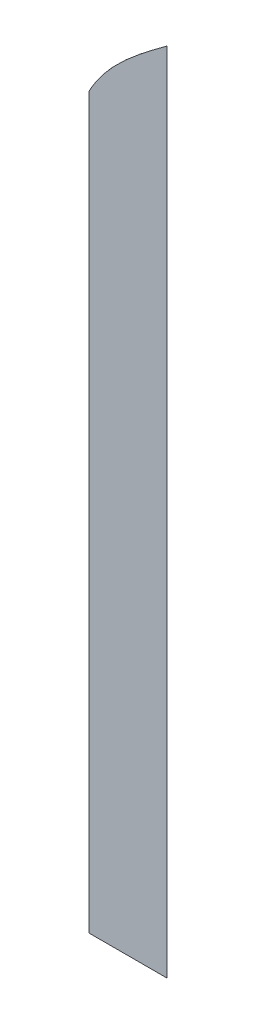
SolidWorks part; units mm, degrees
material "PC High Viscosity"
ref_plane "Front Plane" through (0, 0, 0) normal (0, 0, 1) x (1, 0, 0)
ref_plane "Top Plane" through (0, 0, 0) normal (0, 1, 0) x (1, 0, 0)
ref_plane "Right Plane" through (0, 0, 0) normal (1, 0, 0) x (0, 0, -1)
sketch "Sketch1" plane through (0, 0, 0) normal (0, 0, 1) x (1, 0, 0)
  line L0 (0, 1651) -> (0, 0)
  line L1 (0, 0) -> (-723.9, 0)
  line L4 (-443.5701, 489.6368) -> (-684.6697, 175.2064)
  line L5 (-709.936, 113.4438) -> (-723.9, 0)
  arc A1 (-684.6697, 175.2064) -> (-709.936, 113.4438) centre (-583.8873, 97.9283) ccw
  spline S0 degree 3 poles (-443.5701, 489.6368) (-241.6604, 752.9576) (-282.7431, 676.9444) (0, 1651) knots 0 0 0 0 1 1 1 1
  dimension "D3" = 127
  dimension "D1" = 1651
  dimension "D5" = 114.3
  dimension "D6" = 723.9
extrude "Boss-Extrude1" add sketch "Sketch1" along normal blind 0.127
sketch "Sketch4" plane through (0, 0, 0) normal (0, -1, 0) x (1, 0, 0)
  line L0 (0, 0) -> (-564.7545, 0) construction
  line L1 (-723.9, 0) -> (0, 0) construction
  line L2 (50.8, 50.8) -> (50.8, 177.8)
  line L3 (44.45, 50.8) -> (44.45, 177.8)
  line L4 (44.45, 177.8) -> (50.8, 177.8)
  line L5 (0, 0) -> (0, 6.35)
  arc A0 (0, 0) -> (50.8, 50.8) centre (0, 50.8) ccw
  arc A1 (0, 6.35) -> (44.45, 50.8) centre (0, 50.8) ccw
  point P0 (0, 0)
  dimension "D1" = 50.8
  dimension "D2" = 177.8
  dimension "D3" = 6.35
sketch "Sketch9" plane through (0, 0, 0.127) normal (0, 0, 1) x (1, 0, 0)
  line L0 (200.025, 1879.6) -> (200.025, 0)
  line L1 (200.025, 0) -> (0, 0)
  line L2 (0, 0) -> (0, 1651)
  spline S0 degree 3 poles (0, 1651) (31.1807, 1758.4181) (131.8575, 1828.5211) (200.025, 1879.6) knots 0 0 0 0 1 1 1 1
  spline S1 degree 3 poles (0, 1651) (-282.7431, 676.9444) (-241.6604, 752.9576) (-443.5701, 489.6368) knots 0 0 0 0 1 1 1 1 construction
  dimension "D1" = 200.025
  dimension "D2" = 1879.6
extrude "Boss-Extrude4" add sketch "Sketch9" against normal blind 0.127 separate body
delete or keep bodies "Body-Delete/Keep 1" type delete bodies bodies 101
sketch "Sketch10" plane through (0, 0, 0) normal (0, 0, -1) x (-1, 0, 0)
  line L1 (0, 0) -> (-19.05, 0)
  line L2 (0, 0) -> (0, 1698.1783)
  line L3 (0, 1698.1783) -> (-19.05, 1698.1783)
  line L4 (-19.05, 0) -> (-19.05, 1698.1783)
  spline S0 degree 3 poles (-200.025, 1879.6) (-131.8575, 1828.5211) (-31.1807, 1758.4181) (0, 1651) knots 0 0 0 0 1 1 1 1 construction
  dimension "D1" = 19.05
extrude "Cut-Extrude1" cut sketch "Sketch10" against normal through all
